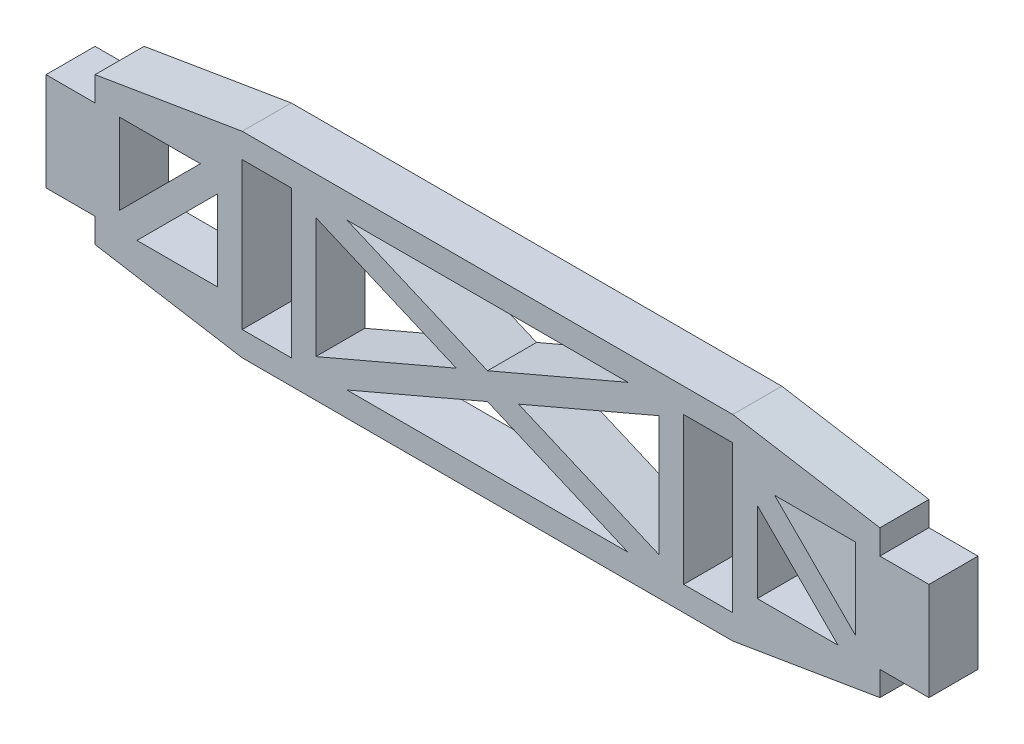
SolidWorks part; units mm, degrees
ref_plane "Front Plane" through (0, 0, 0) normal (0, 0, 1) x (1, 0, 0)
ref_plane "Top Plane" through (0, 0, 0) normal (0, 1, 0) x (1, 0, 0)
ref_plane "Right Plane" through (0, 0, 0) normal (1, 0, 0) x (0, 0, -1)
sketch "Sketch1" plane through (0, 0, 0) normal (0, 0, 1) x (1, 0, 0)
  line L0 (-50.8, -6.35) -> (-50.8, 6.35) construction
  line L1 (-50.8, -9.525) -> (50.8, -9.525) construction
  line L2 (-50.8, -9.525) -> (-50.8, -6.35)
  line L3 (-50.8, 9.525) -> (50.8, 9.525) construction
  line L4 (50.8, -9.525) -> (50.8, -6.35)
  line L5 (-50.8, -9.525) -> (50.8, 9.525) construction
  line L6 (-50.8, 9.525) -> (50.8, -9.525) construction
  line L7 (-50.8, 6.35) -> (-57.15, 6.35)
  line L8 (-50.8, 6.35) -> (-50.8, -6.35) construction
  line L9 (-50.8, -6.35) -> (-57.15, -6.35)
  line L10 (-57.15, 6.35) -> (-57.15, -6.35)
  line L11 (50.8, 6.35) -> (57.15, 6.35)
  line L12 (50.8, 6.35) -> (50.8, -6.35) construction
  line L13 (50.8, -6.35) -> (57.15, -6.35)
  line L14 (57.15, 6.35) -> (57.15, -6.35)
  line L15 (-50.8, 6.35) -> (-50.8, 9.525)
  line L16 (50.8, -6.35) -> (50.8, 6.35) construction
  line L17 (50.8, 6.35) -> (50.8, 9.525)
  line L18 (0, -3.4925) -> (0, 3.4925) construction
  line L19 (-31.75, 9.525) -> (-25.4, 9.525)
  line L20 (-31.75, 9.525) -> (-31.75, -9.525)
  line L21 (-31.75, -9.525) -> (-25.4, -9.525)
  line L22 (-25.4, 9.525) -> (-25.4, -9.525)
  line L23 (31.75, -9.525) -> (25.4, -9.525)
  line L24 (25.4, 9.525) -> (25.4, -9.525)
  line L25 (31.75, 9.525) -> (25.4, 9.525)
  line L26 (31.75, 9.525) -> (31.75, -9.525)
  line L27 (-50.8, 9.525) -> (-31.75, 12.7)
  line L28 (-31.75, 12.7) -> (31.75, 12.7)
  line L29 (31.75, 12.7) -> (50.8, 9.525)
  line L30 (50.8, -9.525) -> (31.75, -12.7)
  line L31 (31.75, -12.7) -> (-31.75, -12.7)
  line L32 (-31.75, -12.7) -> (-50.8, -9.525)
  point P0 (0, 0)
  point P15 (57.15, 0)
  point P16 (-57.15, 0)
  point P26 (-31.75, 0)
  dimension "D1" = 101.6
  dimension "D2" = 6.35
  dimension "D3" = 12.7
  dimension "D4" = 3.175
  dimension "D5" = 50.8
  dimension "D6" = 19.05
  dimension "D7" = 3.175
extrude "Boss-Extrude1" add sketch "Sketch1" along normal mid plane 6.35
sketch "Sketch2" plane through (0, 0, 3.175) normal (0, 0, 1) x (1, 0, 0)
  line L0 (-1000, 0) -> (49000, 0) construction
  line L1 (-47.625, 6.35) -> (-47.625, -6.35)
  line L2 (-47.625, -6.35) -> (-34.925, -6.35)
  line L3 (-34.925, -6.35) -> (-34.925, 6.35)
  line L4 (-34.925, 6.35) -> (-47.625, 6.35)
  line L5 (-50.8, 6.35) -> (-57.15, 6.35) construction
  line L6 (-50.8, 9.525) -> (-50.8, 6.35) construction
  line L7 (-37.1701, 6.35) -> (-47.625, -4.1049)
  line L8 (-50.8, 6.35) -> (-47.625, 6.35) construction
  line L9 (22.225, -9.525) -> (-22.225, -9.525)
  line L10 (22.225, -9.525) -> (22.225, 9.525)
  line L11 (22.225, 9.525) -> (-22.225, 9.525)
  line L12 (-22.225, -9.525) -> (-22.225, 9.525)
  line L13 (22.225, -9.525) -> (-22.225, 9.525) construction
  line L14 (22.225, 9.525) -> (-22.225, -9.525) construction
  line L15 (-34.925, 6.35) -> (-31.75, 6.35) construction
  line L16 (-25.4, 9.525) -> (-22.225, 9.525) construction
  line L17 (22.225, 9.525) -> (25.4, 9.525) construction
  line L18 (-47.625, 6.35) -> (-34.925, -6.35) construction
  line L19 (-34.925, 6.35) -> (-47.625, -6.35) construction
  line L20 (-34.925, 4.1049) -> (-45.3799, -6.35)
  line L21 (-36.0475, 7.4725) -> (-48.7475, -5.2275) construction
  line L22 (-33.8025, 5.2275) -> (-46.5025, -7.4725) construction
  line L23 (22.225, -7.7979) -> (-18.195, 9.525)
  line L24 (18.195, 9.525) -> (-22.225, -7.7979)
  line L25 (18.195, -9.525) -> (-22.225, 7.7979)
  line L26 (22.225, 7.7979) -> (-18.195, -9.525)
  line L27 (22.8503, -8.0659) -> (-21.5997, 10.9841) construction
  line L28 (21.5997, -10.9841) -> (-22.8503, 8.0659) construction
  line L29 (21.5997, 10.9841) -> (-22.8503, -8.0659) construction
  line L30 (22.8503, 8.0659) -> (-21.5997, -10.9841) construction
  line L31 (0, -3.4925) -> (0, 3.4925) construction
  line L32 (37.1701, 6.35) -> (47.625, -4.1049)
  line L33 (34.925, 4.1049) -> (45.3799, -6.35)
  line L34 (34.925, -6.35) -> (34.925, 6.35)
  line L35 (47.625, -6.35) -> (34.925, -6.35)
  line L36 (47.625, 6.35) -> (47.625, -6.35)
  line L37 (34.925, 6.35) -> (47.625, 6.35)
  line L38 (-25.4, -9.525) -> (-25.4, 9.525) construction
  line L39 (-31.75, 9.525) -> (-31.75, -9.525) construction
  point P9 (-47.625, 0)
  point P14 (0, 0)
  dimension "D1" = 3.175
  dimension "D2" = 1.5875
  dimension "D6" = 19.05
  dimension "D3" = 1.5875
  dimension "D4" = 1.5875
  dimension "D5" = 1.5875
extrude "Cut-Extrude1" cut sketch "Sketch2" against normal through all contours L7 L4 L1 | L3 L20 L2 | L24 L25 L12 | L24 L11 L23 | L10 L26 L23 | L25 L26 L9 | L35 L33 L34 | L37 L32 L36 region at (-44.14, 2.865, 3.175) region at (-38.41, -2.865, 3.175) region at (0, -6.9257, 3.175) region at (16.16, 0, 3.175) region at (-16.16, 0, 3.175) region at (0, 6.9257, 3.175) region at (44.14, 2.865, 3.175) region at (38.41, -2.865, 3.175)
